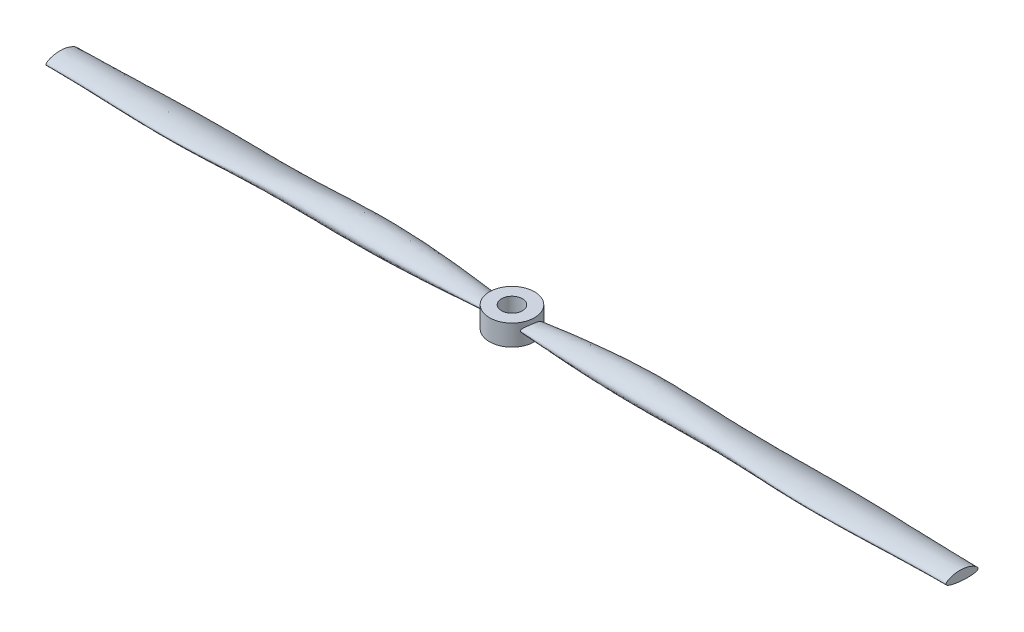
SolidWorks part; units mm, degrees
ref_plane "Front Plane" through (0, 0, 0) normal (0, 0, 1) x (1, 0, 0)
ref_plane "Top Plane" through (0, 0, 0) normal (0, 1, 0) x (1, 0, 0)
ref_plane "Right Plane" through (0, 0, 0) normal (1, 0, 0) x (0, 0, -1)
sketch "Sketch1" plane through (0, 0, 0) normal (0, 1, 0) x (1, 0, 0)
  circle A0 centre (0, 0) radius 7
  circle A1 centre (0, 0) radius 3.25
  dimension "D1" = 14
  dimension "D2" = 6.5
extrude "Boss-Extrude1" add sketch "Sketch1" along normal mid plane 6.5 contours A1 | A0 A1 region at (-6.802, 0, 0) region at (0, 0, 0)
sketch "Sketch2" plane through (0, 0, 0) normal (1, 0, 0) x (0, 0, -1)
  line L0 (-2.8978, 0.7765) -> (2.8978, -0.7765) construction
  line L1 (0, 0) -> (0, 1) construction
  spline S0 degree 3 poles (5.7343, -2.2535) (-5.796, 0.7549) (0.3216, 1.5264) (5.7343, -2.2535) (-5.796, 0.7549) (0.3216, 1.5264) knots -1 -0.763811 -0.487593 0 0.236189 0.512407 1 1.236189 1.512407 2 only from (-2.8978, 0.7765) to (-2.8978, 0.7765)
  point P4 (0, 0)
  dimension "D1" = 1
  dimension "D2" = 6
  dimension "D3" = 105
ref_plane "Plane1" through (46, 0, 0) normal (1, 0, 0) x (0, 0, -1)
ref_plane "Plane2" through (89, 0, 0) normal (1, 0, 0) x (0, 0, -1)
ref_plane "Plane3" through (140, 0, 0) normal (1, 0, 0) x (0, 0, -1)
sketch "Sketch3" plane through (46, 0, 0) normal (1, 0, 0) x (0, 0, -1)
  line L0 (-6.5707, 3.064) -> (6.5707, -3.064) construction
  line L1 (0, 0) -> (0, 5) construction
  spline S0 degree 3 poles (13.0886, -8.9481) (-13.0642, 2.2205) (2.0359, 7.4327) (13.0886, -8.9481) (-13.0642, 2.2205) (2.0359, 7.4327) knots -1 -0.784265 -0.456663 0 0.215735 0.543337 1 1.215735 1.543337 2 only from (-6.5707, 3.064) to (-6.5707, 3.064)
  point P5 (0, 0)
  dimension "D1" = 5
  dimension "D2" = 14.5
  dimension "D3" = 115
sketch "Sketch4" plane through (89, 0, 0) normal (1, 0, 0) x (0, 0, -1)
  line L0 (-7.5175, 2.7362) -> (7.5175, -2.7362) construction
  line L2 (0, 0) -> (0, 3.25) construction
  spline S0 degree 3 poles (14.8621, -7.6284) (-15.0714, 2.8596) (1.3074, 4.8096) (14.8621, -7.6284) (-15.0714, 2.8596) (1.3074, 4.8096) knots -1 -0.772662 -0.48273 0 0.227338 0.51727 1 1.227338 1.51727 2 only from (-7.5175, 2.7362) to (-7.5175, 2.7362)
  point P3 (0, 0)
  dimension "D1" = 3.25
  dimension "D2" = 16
  dimension "D3" = 110
sketch "Sketch5" plane through (140, 0, 0) normal (1, 0, 0) x (0, 0, -1)
  line L0 (-4.981, 0.4358) -> (4.981, -0.4358) construction
  line L2 (0, 0) -> (0, 2) construction
  line L3 (0, 0) -> (0, 1) construction
  spline S0 degree 3 poles (9.8413, -2.2954) (-9.8716, -0.6318) (0.2129, 3.196) (9.8413, -2.2954) (-9.8716, -0.6318) (0.2129, 3.196) knots -1 -0.748582 -0.481569 0 0.251418 0.518431 1 1.251418 1.518431 2 only from (-4.981, 0.4358) to (-4.981, 0.4358)
  point P4 (0, 0)
  dimension "D1" = 2
  dimension "D2" = 10
  dimension "D3" = 95
loft "Loft1" add profiles "Sketch2", "Sketch3", "Sketch4", "Sketch5" connector at (0, -0.3458, -2.7066) connector at (46, 3.0342, -3.6948) connector at (89, 3.5555, 1.2884) connector at (140, 1.7993, -1.3468)
mirror "Mirror1" about plane through (0, 0, 0) normal (1, 0, 0) of "Loft1"
extrude "Cut-Extrude1" cut sketch "Sketch1<3>" along normal up to surface and the other way up to surface contours A1 region at (0, 0, 0) up to face at (0, 3.25, 7) other way up to face at (0, -3.25, 7)
sketch "Sketch1<3>" plane through (0, 0, 0) normal (0, 1, 0) x (1, 0, 0) same geometry as "Sketch1"
